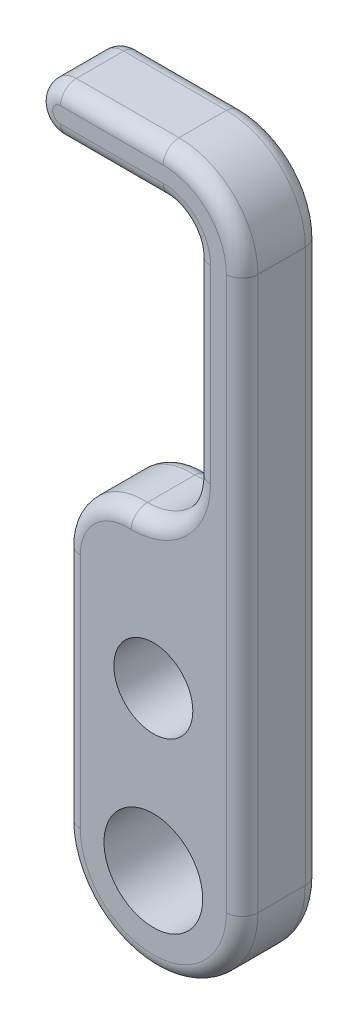
SolidWorks part; units mm, degrees
ref_plane "Front Plane" through (0, 0, 0) normal (0, 0, 1) x (1, 0, 0)
ref_plane "Top Plane" through (0, 0, 0) normal (0, 1, 0) x (1, 0, 0)
ref_plane "Right Plane" through (0, 0, 0) normal (1, 0, 0) x (0, 0, -1)
sketch "Sketch1" [suppressed] plane through (0, 0, 0) normal (0, 0, 1) x (1, 0, 0)
  line L0 (25.1277, -0.5112) -> (27.8541, 37.4911) construction
  line L1 (27.8541, 37.4911) -> (18.3535, 38.1727) construction
  line L2 (18.0023, 0) -> (20.7287, 38.0023) construction
  line L3 (18.3535, 38.1727) -> (15.6271, 0.1704) construction
  line L4 (4.5085, 0) -> (8.3185, 0) construction
  line L5 (-4.5085, 0) -> (4.5085, 0) construction
  line L6 (-4.5085, 0) -> (-4.5085, -50.8) construction
  line L7 (-4.5085, -50.8) -> (4.5085, -50.8) construction
  line L8 (4.5085, 0) -> (4.5085, -50.8) construction
  line L9 (8.3185, 0) -> (8.3185, -50.8) construction
  line L10 (8.3185, -50.8) -> (4.5085, -50.8) construction
  line L11 (15.6271, 0.1704) -> (25.1277, -0.5112) construction
  line L16 (-27.8541, 37.4911) -> (-18.3535, 38.1727) construction
  line L17 (0, 9.525) -> (0, -7.0986) construction
  line L18 (-18.3535, 38.1727) -> (-15.6271, 0.1704) construction
  line L19 (-15.6271, 0.1704) -> (-25.1277, -0.5112) construction
  line L20 (-25.1277, -0.5112) -> (-27.8541, 37.4911) construction
  line L21 (-18.9111, 12.6674) -> (18.9111, 12.6674) construction
  line L22 (-8.3185, -50.8) -> (-4.5085, -50.8) construction
  line L25 (-4.5085, 0) -> (-8.3185, 0) construction
  line L26 (-8.3185, 0) -> (-8.3185, -50.8) construction
  line L32 (-18.0023, 0) -> (-20.7287, 38.0023) construction
  line L48 (12.6181, 13.5168) -> (10.9227, 0.9555) construction
  line L49 (-12.6181, 13.5168) -> (-10.9227, 0.9555) construction
  circle A1 centre (18.0023, 0) radius 7.1438 construction
  circle A3 centre (18.9111, 12.6674) radius 6.35 construction
  circle A4 centre (-18.0023, 0) radius 7.1437 construction
  circle A5 centre (-18.9111, 12.6674) radius 6.35 construction
  point P0 (10.8585, 0)
  point P28 (0, 0)
  point P43 (25.146, 0)
  point P45 (-25.146, 0)
  dimension "D7" = 0
  dimension "D15" = 14.2875
  dimension "D13" = 12.7
  dimension "D14" = 12.7
  dimension "D2" = 2.54
  dimension "D3" = 9.525
  dimension "D4" = 38.1
  dimension "D5" = 16.637
  dimension "D6" = 50.8
  dimension "D8" = 3.81
sketch "Sketch3" plane through (0, 0, 0) normal (0, 0, 1) x (1, 0, 0)
  line L0 (0, 0) -> (0, 12.7) construction
  line L3 (7.1437, 19.05) -> (7.1437, 0)
  line L4 (7.1437, 19.05) -> (7.1438, 44.45)
  line L5 (0.7937, 50.8) -> (0.7937, 46.99) construction
  line L6 (3.3337, 44.45) -> (3.3338, 29.21)
  line L7 (-7.1438, 0) -> (-7.1438, 19.05)
  line L8 (0.7937, 50.8) -> (-7.4613, 50.8)
  line L10 (-7.4613, 46.99) -> (0.7937, 46.99)
  circle A0 centre (0, 0) radius 3.9688
  arc A1 (7.1437, 0) -> (-7.1438, 0) centre (0, 0) cw
  circle A2 centre (0, 12.7) radius 3.175
  circle A4 centre (0, 0) radius 7.1438 construction
  arc A5 (7.1438, 44.45) -> (0.7937, 50.8) centre (0.7937, 44.45) ccw
  arc A6 (0.7937, 46.99) -> (3.3337, 44.45) centre (0.7937, 44.45) cw
  arc A7 (3.3338, 29.21) -> (-1.7462, 24.13) centre (-1.7463, 29.21) cw
  arc A9 (-1.7462, 24.13) -> (-7.1438, 19.05) centre (-2.0544, 19.05) ccw
  arc A10 (-7.4613, 50.8) -> (-7.4613, 46.99) centre (-7.4613, 48.895) ccw
  dimension "D1" = 7.1437
  dimension "D2" = 14.2875
  dimension "D3" = 6.35
  dimension "D4" = 7.9375
  dimension "D5" = 12.7
  dimension "D6" = 180
  dimension "D13" = 90
  dimension "D14" = 5.08
  dimension "D7" = 25.4
  dimension "D8" = 6.35
  dimension "D9" = 90
  dimension "D10" = 3.81
  dimension "D11" = 90
  dimension "D12" = 15.24
  dimension "D15" = 6.35
  dimension "D16" = 8.255
extrude "Boss-Extrude1" add sketch "Sketch3" along normal blind 6.35
fillet "Fillet2" radius 1.27 22 edges at (7.1438, 22.225, 0) (5.2839, 48.9401, 0) (-3.3338, 50.8, 0) (-9.3663, 48.895, 0) (-3.3338, 46.99, 0) (2.5898, 46.2461, 0) (3.3338, 36.83, 0) (1.8459, 25.6179, 0) (-5.5425, 22.7561, 0) (-7.1438, 9.525, 0) (0, -7.1438, 0) (-7.1438, 9.525, 6.35) (-5.5425, 22.7561, 6.35) (1.8459, 25.6179, 6.35) (3.3338, 36.83, 6.35) (2.5898, 46.2461, 6.35) (-3.3338, 46.99, 6.35) (-9.3663, 48.895, 6.35) (-3.3338, 50.8, 6.35) (5.2839, 48.9401, 6.35) (7.1438, 22.225, 6.35) (0, -7.1438, 6.35)
